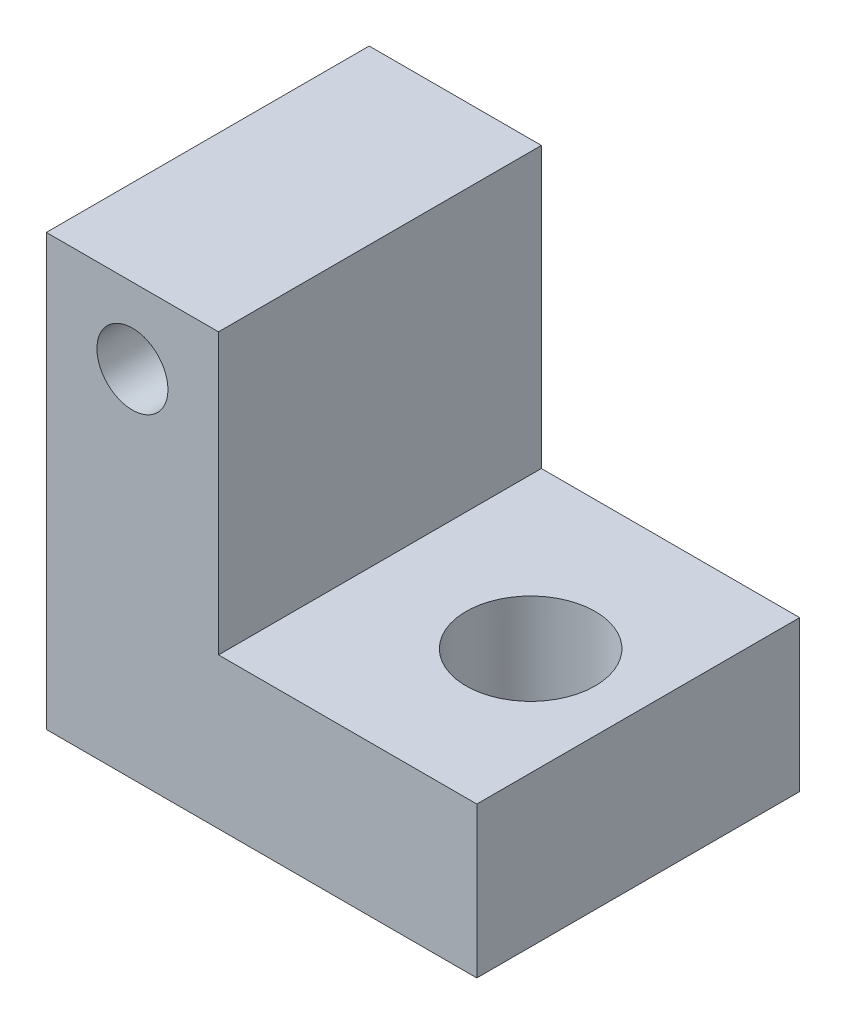
SolidWorks part; units mm, degrees
ref_plane "Piano frontale" through (0, 0, 0) normal (0, 0, 1) x (1, 0, 0)
ref_plane "Piano superiore" through (0, 0, 0) normal (0, 1, 0) x (1, 0, 0)
ref_plane "Piano destro" through (0, 0, 0) normal (1, 0, 0) x (0, 0, -1)
sketch "Schizzo1" plane through (0, 0, 0) normal (0, 0, 1) x (1, 0, 0)
  line L0 (0, 0) -> (-20, 0)
  line L1 (-20, 0) -> (-20, 20)
  line L2 (-20, 20) -> (-12, 20)
  line L3 (-12, 20) -> (-12, 7)
  line L4 (-12, 7) -> (0, 7)
  line L5 (0, 7) -> (0, 0)
  dimension "D1" = 20
  dimension "D2" = 12
  dimension "D3" = 20
  dimension "D4" = 7
extrude "Estrusione-Estrusione1" add sketch "Schizzo1" along normal blind 15
sketch "Schizzo2" plane through (0, 0, 0) normal (0, -1, 0) x (1, 0, 0)
  line L0 (0, 7.5) -> (-20, 7.5) construction
  line L1 (0, 15) -> (0, 0) construction
  line L2 (-20, 15) -> (-20, 0) construction
  circle A0 centre (-5, 7.5) radius 3
  dimension "D1" = 6
  dimension "D2" = 5
extrude "Taglio-Estrusione1" cut sketch "Schizzo2" against normal blind 15
sketch "Schizzo3" plane through (0, 0, 15) normal (0, 0, 1) x (1, 0, 0)
  line L0 (-16, 20) -> (-16, 0) construction
  line L1 (-12, 20) -> (-20, 20) construction
  line L2 (-20, 0) -> (0, 0) construction
  point P6 (-16, 16.5)
  dimension "D1" = 16.5
hole_wizard "Foro filettato M4-1" positions "Schizzo5" profile "Schizzo4" tap size "M4" standard "ISO" end condition through all
sketch "Schizzo5" plane through (0, 0, 15) normal (0, 0, 1) x (1, 0, 0)
  point P0 (-16, 16.5)
cosmetic thread "Filettatura del foro1" parameters "D2"=4
sketch "Schizzo4" plane through (-16, 16.5, 15) normal (1, 0, 0) x (0, -1, 0)
  line L0 (0, 0) -> (0, 15)
  line L1 (0, 15) -> (1.65, 15)
  line L2 (1.65, 15) -> (1.65, 0)
  line L5 (1.65, 0) -> (0, 0)
  line L11 (0, -6.35) -> (0, 107.95) construction
  dimension "Thru Tap Drill Dia." = 3.3
  dimension "Thru Tap Drill Depth" = 15
